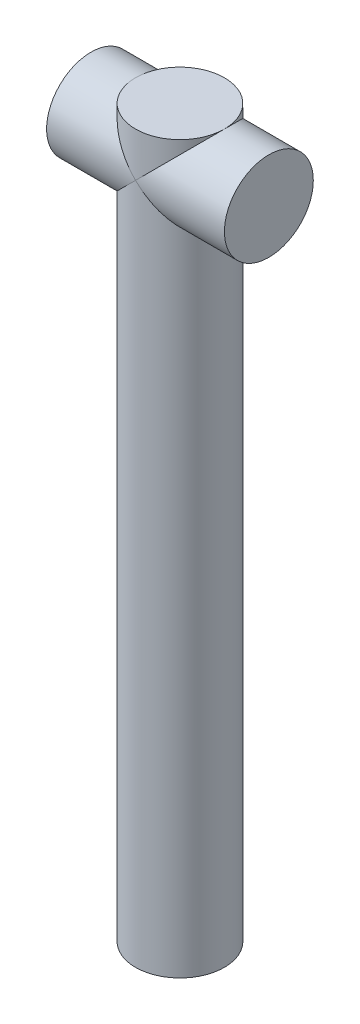
SolidWorks part; units mm, degrees
ref_plane "Plano frontal" through (0, 0, 0) normal (0, 0, 1) x (1, 0, 0)
ref_plane "Plano superior" through (0, 0, 0) normal (0, 1, 0) x (1, 0, 0)
ref_plane "Plano direito" through (0, 0, 0) normal (1, 0, 0) x (0, 0, -1)
sketch "Esboço1" plane through (0, 0, 0) normal (0, 1, 0) x (1, 0, 0)
  circle A0 centre (0, 0) radius 15
  dimension "D1" = 30
extrude "Ressalto-extrusão1" add sketch "Esboço1" against normal blind 245
sketch "Esboço3" plane through (0, 0, 0) normal (1, 0, 0) x (0, 0, -1)
  line L0 (15, -245) -> (15, 0) construction
  line L1 (15, 0) -> (-15, 0) construction
  circle A0 centre (0, -15) radius 15
  dimension "D1" = 30
extrude "Ressalto-extrusão2" add sketch "Esboço3" along normal blind 30 and the other way blind 30
